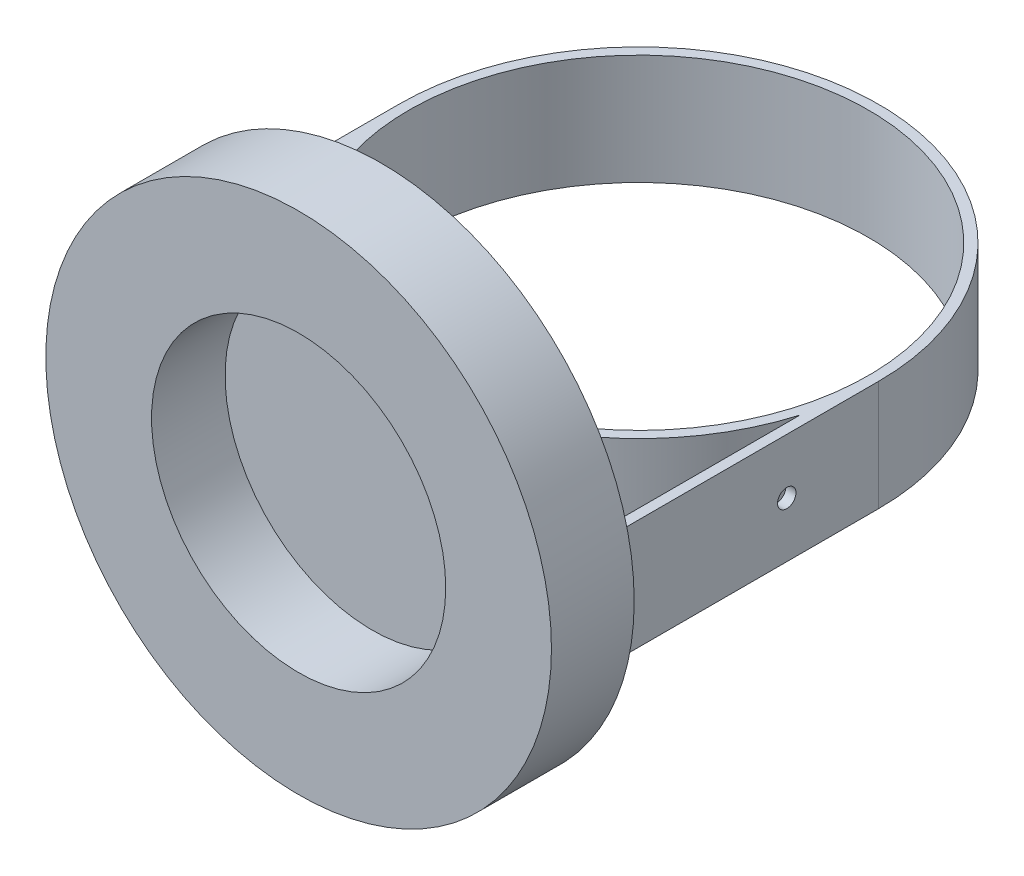
SolidWorks part; units mm, degrees
ref_plane "Front Plane" through (0, 0, 0) normal (0, 0, 1) x (1, 0, 0)
ref_plane "Top Plane" through (0, 0, 0) normal (0, 1, 0) x (1, 0, 0)
ref_plane "Right Plane" through (0, 0, 0) normal (1, 0, 0) x (0, 0, -1)
sketch "Sketch1" plane through (0, 0, 0) normal (0, 0, 1) x (1, 0, 0)
  circle A0 centre (0, 0) radius 27.5
  dimension "D1" = 55
extrude "Boss-Extrude1" add sketch "Sketch1" along normal blind 1
sketch "Sketch2" plane through (0, 0, 1) normal (0, 0, 1) x (1, 0, 0)
  circle A0 centre (0, 0) radius 16
  circle A1 centre (0, 0) radius 27.5
  dimension "D1" = 55
  dimension "D2" = 32
extrude "Boss-Extrude2" add sketch "Sketch2" along normal blind 8
sketch "Sketch3" plane through (0, 0, 0) normal (0, 0, -1) x (-1, 0, 0)
  line L0 (-10.9886, 0) -> (10.4466, 0) construction
  line L1 (0, 10.2261) -> (0, -10.3215) construction
  line L2 (-26.0952, -6) -> (-26.0952, 6)
  line L3 (-25, -6) -> (-25, 6)
  line L4 (-25, 6) -> (-26.0952, 6)
  line L5 (-25, -6) -> (-26.0952, -6)
  line L6 (25, -6) -> (26.0952, -6)
  line L7 (25, 6) -> (26.0952, 6)
  line L8 (26.0952, -6) -> (26.0952, 6)
  line L9 (25, -6) -> (25, 6)
  point P13 (-26.0952, 0)
  point P14 (-25, 0)
  dimension "D1" = 25
  dimension "D3" = 6
extrude "Boss-Extrude3" add sketch "Sketch3" along normal blind 28
sketch "Sketch6" plane through (0, 0, 0) normal (0, 1, 0) x (1, 0, 0)
  arc A0 (-26.0952, 28) -> (26.0952, 28) centre (0, 28) cw
  arc A1 (-25, 28) -> (25, 28) centre (0, 28) cw
  arc A2 (-25, 28) -> (25, 28) centre (0, 28) ccw
  arc A3 (-26.0952, 28) -> (26.0952, 28) centre (0, 28) ccw
extrude "Boss-Extrude4" add sketch "Sketch6" along normal blind 6 and the other way blind 6
sketch "Sketch4" plane through (0, 0, 0) normal (1, 0, 0) x (0, 0, -1)
  line L2 (0, -27.5) -> (0, 27.5) construction
  circle A0 centre (18, 0) radius 1
  point P2 (18, 0)
  dimension "D1" = 2
  dimension "D3" = 18
extrude "Cut-Extrude1" cut sketch "Sketch4" against normal through all both and the other way through all
